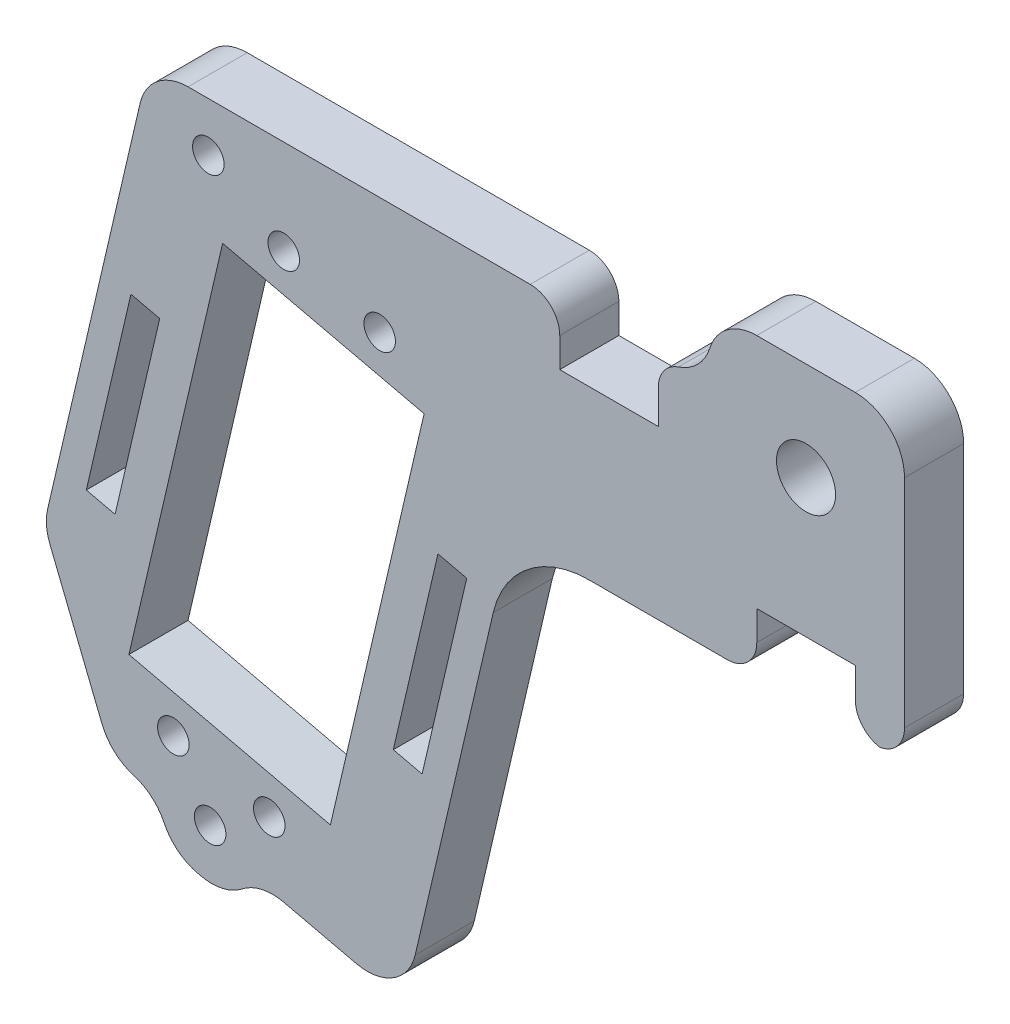
SolidWorks part; units mm, degrees
material "MDF"
ref_plane "Plano frontal" through (0, 0, 0) normal (0, 0, 1) x (1, 0, 0)
ref_plane "Plano superior" through (0, 0, 0) normal (0, 1, 0) x (1, 0, 0)
ref_plane "Plano direito" through (0, 0, 0) normal (1, 0, 0) x (0, 0, -1)
sketch "Esboço1" plane through (0, 0, 0) normal (0, 0, 1) x (1, 0, 0)
  line L0 (0, 20) -> (0, 0) construction
  line L5 (15, 16) -> (18, 16) construction
  line L6 (18, 6) -> (18, 16) construction
  line L15 (10, 11) -> (-10, 11) construction
  line L16 (15, 6) -> (18, 6) construction
  line L21 (-15, 6) -> (-18, 6) construction
  line L22 (-15, 6) -> (-15, 16) construction
  line L27 (-15, 16) -> (-18, 16) construction
  line L28 (-18, 6) -> (-18, 16) construction
  line L29 (-15, 6) -> (-18, 16) construction
  line L30 (-15, 16) -> (-18, 6) construction
  line L35 (15, 6) -> (15, 16) construction
  line L36 (23, 0) -> (23, 23)
  line L37 (23, 23) -> (-66.701, 23)
  line L43 (-29.9553, 0) -> (23, 0)
  line L61 (-68.7379, -29.9136) -> (-59.2257, 10.995)
  line L66 (-59.2257, 10.995) -> (-38.7714, 6.2389)
  line L67 (-38.7714, 6.2389) -> (-48.2836, -34.6697)
  line L68 (-48.2836, -34.6697) -> (-68.7379, -29.9136)
  line L69 (-63.9818, -9.4593) -> (-43.5275, -14.2154) construction
  line L74 (-48.9985, 8.617) -> (-58.5107, -32.2917) construction
  line L75 (-61.7051, 0.3321) -> (-41.2508, -4.424) construction
  line L80 (-38.7714, 6.2389) -> (-38.7714, -27.2218) construction
  line L85 (0, 20) -> (-15.8727, -48.263) construction
  line L86 (5, 0) -> (-5, 0)
  line L87 (-66.701, 23) -> (-80.7429, -37.389)
  line L88 (-80.7429, -37.389) -> (-40.8082, -46.6747)
  line L89 (-40.8082, -46.6747) -> (-29.9553, 0)
  line L93 (-65.6456, -40.8994) -> (-66.4949, -44.552)
  line L94 (-66.4949, -44.552) -> (-56.7548, -46.8168)
  line L95 (-55.9055, -43.1642) -> (-56.7548, -46.8168)
  line L96 (-47.0168, 17.1396) -> (-48.1492, 12.2695) construction
  line L97 (-48.1492, 12.2695) -> (-53.0193, 13.4019) construction
  line L98 (5, 0) -> (5, 6)
  line L99 (5, 6) -> (-5, 6)
  line L100 (-5, 0) -> (-5, 6)
  line L101 (0, 6) -> (0, 0) construction
  line L102 (5, 3) -> (-5, 3) construction
  line L103 (-10, 23) -> (-10, 30)
  line L104 (-10, 30) -> (10, 30)
  line L105 (10, 30) -> (10, 23)
  line L106 (10, 23) -> (10, 0)
  line L107 (-73.0647, -17.6141) -> (-70.1427, -18.2935)
  line L108 (-70.1427, -18.2935) -> (-65.6131, 1.1868)
  line L109 (-65.6131, 1.1868) -> (-68.5351, 1.8662)
  line L110 (-38.9742, -25.5409) -> (-41.8962, -24.8615)
  line L111 (-37.3666, -5.3812) -> (-34.4446, -6.0606)
  line L112 (-41.8962, -24.8615) -> (-37.3666, -5.3812)
  line L113 (-68.5351, 1.8662) -> (-73.0647, -17.6141)
  line L114 (-15, 17) -> (-25, 17)
  line L115 (-15, 17) -> (-15, 23)
  line L116 (-15, 23) -> (-25, 23)
  line L117 (-25, 17) -> (-25, 23)
  line L118 (-20, 23) -> (-20, 17) construction
  line L119 (-15, 20) -> (-25, 20) construction
  line L120 (-34.4446, -6.0606) -> (-38.9742, -25.5409)
  circle A0 centre (0, 20) radius 3
  circle A1 centre (10, 11) radius 1.6 construction
  circle A2 centre (-10, 11) radius 1.6 construction
  circle A8 centre (-64.2301, -34.8118) radius 1.6
  circle A9 centre (-54.49, -37.0766) radius 1.6
  circle A10 centre (-43.2792, 11.1371) radius 1.6
  circle A11 centre (-53.0193, 13.4019) radius 1.6
  circle A12 centre (-47.0168, 17.1396) radius 1.6 construction
  circle A15 centre (-60.4925, -40.8143) radius 1.6
  circle A16 centre (-60.6769, 18) radius 1.6
  point P0 (0, 20)
  point P13 (-16.5, 11)
  point P39 (-51.4779, -2.046)
  point P49 (0, 3)
  point P61 (0, 11)
  point P62 (-67.8779, -8.5534)
  point P68 (0, 30)
  point P69 (-20, 20)
  dimension "D1" = 6
  dimension "D3" = 3.2
  dimension "D11" = 14.6974
  dimension "D12" = 56
  dimension "D9" = 49.5
  dimension "D30" = 5
  dimension "D33" = 5
  dimension "D34" = 7
  dimension "D2" = 20
  dimension "D4" = 5
  dimension "D5" = 21
  dimension "D6" = 10
  dimension "D7" = 3
  dimension "D8" = 42
  dimension "D10" = 10
  dimension "D13" = 20
  dimension "D14" = 10
  dimension "D15" = 10
  dimension "D16" = 10
  dimension "D17" = 6
  dimension "D18" = 5
  dimension "D19" = 7
  dimension "D20" = 6
  dimension "D21" = 13.09
  dimension "D22" = 10
  dimension "D23" = 10
  dimension "D24" = 5
  dimension "D25" = 5
  dimension "D26" = 20
  dimension "D27" = 3
  dimension "D28" = 20
  dimension "D32" = 4
extrude "Ressalto-extrusão1" add sketch "Esboço1" along normal blind 6 contours L37 L87 L88 L89 L43 A12 A9 A8 A0 L67 L68 L61 L66 L21 L28 L27 L22 L86 L100 L99 L98 A10 A11 | L104 L103 L37 | L95 L88 L93 L94 A15 region at (-39.2331, -2.5515, 0) region at (0, 26.5, 0) region at (-61.2053, -43.8799, 0)
fillet "Filete1" radius 10 1 edges at (-29.9553, 0, 3)
fillet "Filete2" radius 5 6 edges at (-66.701, 23, 3) (-66.4949, -44.552, 3) (-56.7548, -46.8168, 3) (-40.8082, -46.6747, 3) (-10, 30, 3) (10, 30, 3)
fillet "Filete4" radius 5 3 edges at (-65.6456, -40.8994, 3) (-55.9055, -43.1642, 3) (-10, 23, 3)
fillet "Filete5" radius 3 5 edges at (-25, 23, 3) (-15, 23, 3) (-5, 0, 3) (10, 0, 3) (5, 0, 3)
chamfer "Chanfro1" distance 15 angle 35 1 edges at (-80.7429, -37.389, 3) first distance on face at (-74.1716, -9.1283, 3)
fillet "Filete6" radius 5 2 edges at (-77.3457, -22.7787, 3) (-70.5127, -39.7677, 3)
